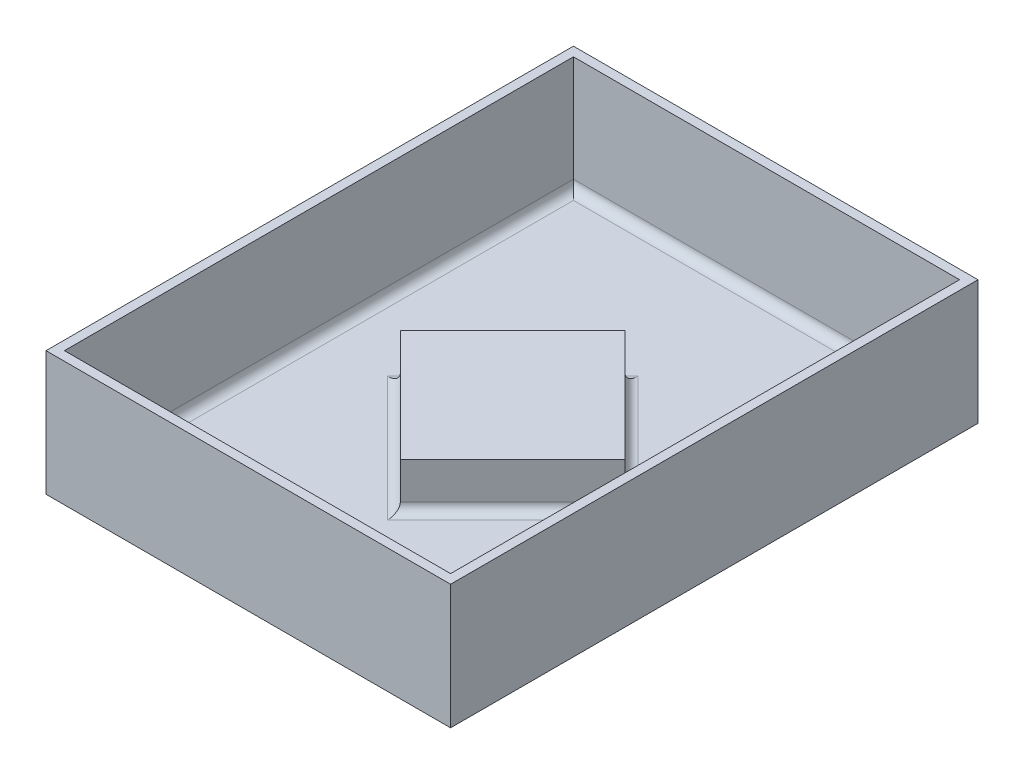
SolidWorks part; units mm, degrees
ref_plane "Front Plane" through (0, 0, 0) normal (0, 0, 1) x (1, 0, 0)
ref_plane "Top Plane" through (0, 0, 0) normal (0, 1, 0) x (1, 0, 0)
ref_plane "Right Plane" through (0, 0, 0) normal (1, 0, 0) x (0, 0, -1)
sketch "Sketch1" plane through (0, 0, 0) normal (0, 1, 0) x (1, 0, 0)
  line L0 (0, 276.225) -> (419.1, 276.225) construction
  line L1 (0, 0) -> (419.1, 0) construction
  line L2 (0, 0) -> (0, 552.45) construction
  line L3 (0, 552.45) -> (419.1, 552.45) construction
  line L4 (419.1, 0) -> (419.1, 552.45) construction
  line L5 (209.55, 154.9915) -> (330.7835, 276.225) construction
  line L6 (209.55, 154.9915) -> (88.3165, 276.225) construction
  line L7 (88.3165, 276.225) -> (209.55, 397.4585) construction
  line L8 (330.7835, 276.225) -> (209.55, 397.4585) construction
  line L9 (209.55, 397.4585) -> (209.55, 276.225) construction
  line L10 (209.55, 276.225) -> (209.55, 154.9915) construction
  line L13 (209.55, 0) -> (209.55, 154.9915) construction
  line L16 (209.55, 397.4585) -> (209.55, 552.45) construction
sketch "Sketch2" plane through (0, 0, 0) normal (0, 1, 0) x (1, 0, 0)
  line L1 (0, 552.45) -> (419.1, 552.45)
  line L2 (0, 552.45) -> (0, 0)
  line L3 (0, 0) -> (419.1, 0)
  line L4 (419.1, 552.45) -> (419.1, 0)
  line L5 (-10, 562.45) -> (429.1, 562.45)
  line L6 (-10, 562.45) -> (-10, -10)
  line L7 (-10, -10) -> (429.1, -10)
  line L8 (429.1, 562.45) -> (429.1, -10)
extrude "Boss-Extrude1" add sketch "Sketch2" along normal blind 125
sketch "Sketch3" plane through (0, 0, 0) normal (0, 1, 0) x (1, 0, 0)
  line L0 (88.3165, 276.225) -> (209.55, 154.9915)
  line L1 (88.3165, 276.225) -> (210.2221, 398.1306)
  line L2 (209.55, 154.9915) -> (331.4556, 276.8971)
  line L3 (210.2221, 398.1306) -> (331.4556, 276.8971)
extrude "Boss-Extrude2" add sketch "Sketch3" along normal blind 50 separate body
sketch "Sketch4" plane through (0, 0, 0) normal (0, 1, 0) x (1, 0, 0)
  line L1 (429.1, -10) -> (-10, -10)
  line L2 (429.1, -10) -> (429.1, 562.45)
  line L3 (429.1, 562.45) -> (-10, 562.45)
  line L4 (-10, -10) -> (-10, 562.45)
extrude "Boss-Extrude3" add sketch "Sketch4" against normal blind 10
fillet "Fillet1" radius 10 8 edges at (270.5028, 0, -215.9443) (270.8388, 0, -337.5138) (149.2693, 0, -337.1778) (148.9333, 0, -215.6083) (419.1, 0, -276.225) (209.55, 0, 0) (0, 0, -276.225) (209.55, 0, -552.45)
ref_axis "Axis1" through (209.55, 375.562, -276.225) along (0, -1, 0)
